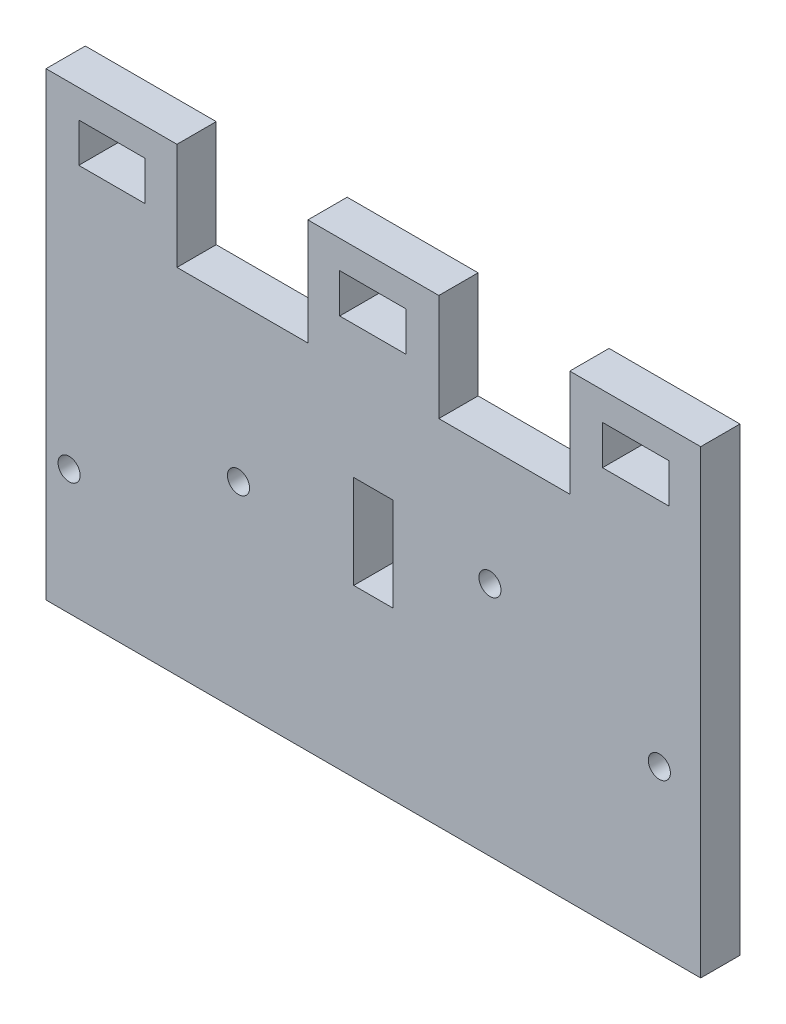
SolidWorks part; units mm, degrees
ref_plane "Front Plane" through (0, 0, 0) normal (0, 0, 1) x (1, 0, 0)
ref_plane "Top Plane" through (0, 0, 0) normal (0, 1, 0) x (1, 0, 0)
ref_plane "Right Plane" through (0, 0, 0) normal (1, 0, 0) x (0, 0, -1)
sketch "Sketch1" plane through (0, 0, 0) normal (0, 0, 1) x (1, 0, 0)
  line L1 (-39.3603, 14.4208) -> (49.5397, 14.4208)
  line L2 (-39.3603, 14.4208) -> (-39.3603, -48.0632)
  line L3 (-39.3603, -48.0632) -> (49.5397, -48.0632)
  line L4 (49.5397, 14.4208) -> (49.5397, -48.0632)
  dimension "D1" = 88.9
  dimension "D2" = 62.484
extrude "Boss-Extrude1" add sketch "Sketch1" along normal blind 5.334
sketch "Sketch2" plane through (0, 0, 5.334) normal (0, 0, 1) x (1, 0, 0)
  line L0 (49.5397, 14.4208) -> (-39.3603, 14.4208) construction
  line L1 (-21.5803, 14.4208) -> (-3.8003, 14.4208)
  line L2 (-21.5803, 14.4208) -> (-21.5803, -0.0572)
  line L3 (-21.5803, -0.0572) -> (-3.8003, -0.0572)
  line L4 (-3.8003, 14.4208) -> (-3.8003, -0.0572)
  line L5 (-21.5803, -0.0572) -> (-39.3603, -0.0572) construction
  line L6 (13.9797, 14.4208) -> (31.7597, 14.4208)
  line L7 (13.9797, 14.4208) -> (13.9797, -0.0572)
  line L8 (13.9797, -0.0572) -> (31.7597, -0.0572)
  line L9 (31.7597, 14.4208) -> (31.7597, -0.0572)
  line L10 (-39.3603, 14.4208) -> (-39.3603, -48.0632) construction
  line L11 (-3.8003, -0.0572) -> (13.9797, -0.0572) construction
  line L12 (31.7597, -0.0572) -> (49.5397, -0.0572) construction
  line L13 (49.5397, -48.0632) -> (49.5397, 14.4208) construction
  dimension "D1" = 14.478
extrude "Cut-Extrude1" cut sketch "Sketch2" against normal through all
sketch "Sketch3" plane through (0, 0, 5.334) normal (0, 0, 1) x (1, 0, 0)
  line L0 (-21.5803, 14.4208) -> (-39.3603, 14.4208) construction
  line L1 (-34.9153, 10.6108) -> (-25.8983, 10.6108)
  line L2 (-34.9153, 10.6108) -> (-34.9153, 5.2768)
  line L3 (-34.9153, 5.2768) -> (-25.8983, 5.2768)
  line L4 (-25.8983, 10.6108) -> (-25.8983, 5.2768)
  line L6 (-39.3603, 14.4208) -> (-39.3603, -48.0632) construction
  line L7 (-21.5803, 14.4208) -> (-21.5803, -0.0572) construction
  line L8 (-12.6903, -0.0572) -> (-12.6903, 17.5431) construction
  line L9 (-21.5803, -0.0572) -> (-3.8003, -0.0572) construction
  line L10 (22.8697, -0.0572) -> (22.8697, 18.5459) construction
  line L11 (13.9797, -0.0572) -> (31.7597, -0.0572) construction
  line L12 (0.5177, 10.6108) -> (0.5177, 5.2768)
  line L13 (9.5347, 5.2768) -> (0.5177, 5.2768)
  line L14 (9.5347, 10.6108) -> (9.5347, 5.2768)
  line L15 (9.5347, 10.6108) -> (0.5177, 10.6108)
  line L16 (36.2047, 10.6108) -> (45.2217, 10.6108)
  line L17 (36.2047, 10.6108) -> (36.2047, 5.2768)
  line L18 (36.2047, 5.2768) -> (45.2217, 5.2768)
  line L19 (45.2217, 10.6108) -> (45.2217, 5.2768)
  dimension "D1" = 3.81
  dimension "D2" = 5.334
  dimension "D3" = 4.445
  dimension "D4" = 4.318
extrude "Cut-Extrude2" cut sketch "Sketch3" against normal through all
sketch "Sketch5" plane through (0, 0, 5.334) normal (0, 0, 1) x (1, 0, 0)
  line L0 (5.0897, 14.4208) -> (5.0897, -48.0632) construction
  line L1 (2.4227, -12.7572) -> (7.7567, -12.7572)
  line L2 (2.4227, -12.7572) -> (2.4227, -25.4572)
  line L3 (2.4227, -25.4572) -> (7.7567, -25.4572)
  line L4 (7.7567, -12.7572) -> (7.7567, -25.4572)
  line L5 (13.9797, 14.4208) -> (-3.8003, 14.4208) construction
  line L6 (-39.3603, -48.0632) -> (49.5397, -48.0632) construction
  line L7 (13.9797, -0.0572) -> (31.7597, -0.0572) construction
  dimension "D1" = 5.334
  dimension "D2" = 12.7
  dimension "D3" = 12.7
  dimension "D4" = 2.667
extrude "Cut-Extrude3" cut sketch "Sketch5" against normal through all
sketch "Sketch6" plane through (0, 0, 5.334) normal (0, 0, 1) x (1, 0, 0)
  line L12 (13.9797, -0.0572) -> (13.9797, 14.4208)
  line L13 (13.9797, 14.4208) -> (-3.8003, 14.4208)
  line L14 (-3.8003, 14.4208) -> (-3.8003, -0.0572)
  line L15 (-3.8003, -0.0572) -> (-21.5803, -0.0572)
  line L16 (-21.5803, -0.0572) -> (-21.5803, 14.4208)
  line L17 (-21.5803, 14.4208) -> (-39.3603, 14.4208)
  line L18 (-39.3603, 14.4208) -> (-39.3603, -48.0632)
  line L19 (-39.3603, -48.0632) -> (49.5397, -48.0632)
  line L20 (49.5397, -48.0632) -> (49.5397, 14.4208)
  line L21 (49.5397, 14.4208) -> (31.7597, 14.4208)
  line L22 (31.7597, 14.4208) -> (31.7597, -0.0572)
  line L23 (31.7597, -0.0572) -> (13.9797, -0.0572)
  line L24 (13.9797, -0.0572) -> (13.9797, 14.4208)
  line L25 (13.9797, 14.4208) -> (-3.8003, 14.4208)
  line L26 (-3.8003, 14.4208) -> (-3.8003, -0.0572)
  line L27 (-3.8003, -0.0572) -> (-21.5803, -0.0572)
  line L28 (-21.5803, -0.0572) -> (-21.5803, 14.4208)
  line L29 (-21.5803, 14.4208) -> (-39.3603, 14.4208)
  line L30 (-39.3603, 14.4208) -> (-39.3603, -48.0632)
  line L31 (-39.3603, -48.0632) -> (49.5397, -48.0632)
  line L32 (49.5397, -48.0632) -> (49.5397, 14.4208)
  line L33 (49.5397, 14.4208) -> (31.7597, 14.4208)
  line L34 (31.7597, 14.4208) -> (31.7597, -0.0572)
  line L35 (31.7597, -0.0572) -> (13.9797, -0.0572)
  dimension "D1" = 0
sketch "Sketch7" plane through (0, 0, 5.334) normal (0, 0, 1) x (1, 0, 0)
  line L12 (13.9797, -0.0572) -> (13.9797, 14.4208)
  line L13 (13.9797, 14.4208) -> (-3.8003, 14.4208)
  line L14 (-3.8003, 14.4208) -> (-3.8003, -0.0572)
  line L15 (-3.8003, -0.0572) -> (-21.5803, -0.0572)
  line L16 (-21.5803, -0.0572) -> (-21.5803, 14.4208)
  line L17 (-21.5803, 14.4208) -> (-39.3603, 14.4208)
  line L18 (-39.3603, 14.4208) -> (-39.3603, -48.0632)
  line L19 (-39.3603, -48.0632) -> (49.5397, -48.0632)
  line L20 (49.5397, -48.0632) -> (49.5397, 14.4208)
  line L21 (49.5397, 14.4208) -> (31.7597, 14.4208)
  line L22 (31.7597, 14.4208) -> (31.7597, -0.0572)
  line L23 (31.7597, -0.0572) -> (13.9797, -0.0572)
  line L24 (13.9797, -0.0572) -> (13.9797, 14.4208)
  line L25 (13.9797, 14.4208) -> (-3.8003, 14.4208)
  line L26 (-3.8003, 14.4208) -> (-3.8003, -0.0572)
  line L27 (-3.8003, -0.0572) -> (-21.5803, -0.0572)
  line L28 (-21.5803, -0.0572) -> (-21.5803, 14.4208)
  line L29 (-21.5803, 14.4208) -> (-39.3603, 14.4208)
  line L30 (-39.3603, 14.4208) -> (-39.3603, -48.0632)
  line L31 (-39.3603, -48.0632) -> (49.5397, -48.0632)
  line L32 (49.5397, -48.0632) -> (49.5397, 14.4208)
  line L33 (49.5397, 14.4208) -> (31.7597, 14.4208)
  line L34 (31.7597, 14.4208) -> (31.7597, -0.0572)
  line L35 (31.7597, -0.0572) -> (13.9797, -0.0572)
  circle A0 centre (-36.2253, -31.0912) radius 1.5 construction
  circle A1 centre (-13.2253, -21.0912) radius 1.5 construction
  circle A2 centre (20.9247, -16.0112) radius 1.5 construction
  circle A3 centre (43.9247, -26.0112) radius 1.5 construction
  circle A4 centre (-36.2253, -31.0912) radius 1.5
  circle A5 centre (-13.2253, -21.0912) radius 1.5
  circle A6 centre (20.9247, -16.0112) radius 1.5
  circle A7 centre (43.9247, -26.0112) radius 1.5
  dimension "D1" = 0
extrude "Cut-Extrude4" cut sketch "Sketch7" against normal through all contours A4 | A6 | A7 | A5 region at (-36.2253, -31.0912, 5.334) region at (20.9247, -16.0112, 5.334) region at (43.9247, -26.0112, 5.334)
equation "\"MDF\"= .21in"
equation "\"Foamcore\"= .13in"
equation "\"Gmaterial\"= \"MDF\""
equation "\"D1@Boss-Extrude1\"=\"MDF\""
equation "\"D1@Sketch2\"=2*\"MDF\"+.15"
equation "\"D2@Sketch3\"=\"MDF\""
equation "\"D1@Sketch5\"=\"MDF\""
equation "\"D4@Sketch5\"=\"MDF\"/2"
